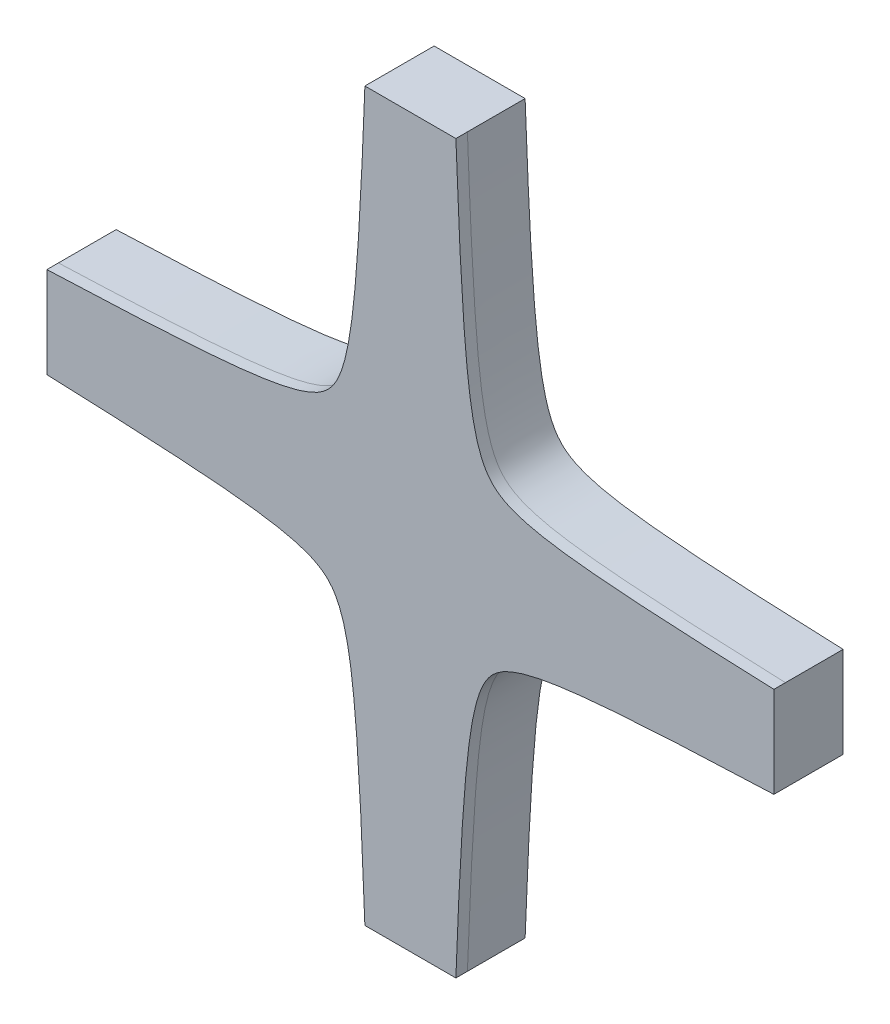
SolidWorks part; units mm, degrees
ref_plane "Front Plane" through (0, 0, 0) normal (0, 0, 1) x (1, 0, 0)
ref_plane "Top Plane" through (0, 0, 0) normal (0, 1, 0) x (1, 0, 0)
ref_plane "Right Plane" through (0, 0, 0) normal (1, 0, 0) x (0, 0, -1)
sketch "Sketch1" plane through (0, 0, 0) normal (0, 0, 1) x (1, 0, 0)
  line L0 (-66.0929, 6.6772) -> (-66.0929, 14.5621)
  line L1 (-66.0929, 6.6772) -> (-66.0929, -1.2077)
  line L2 (-3.0929, -56.3228) -> (-10.9779, -56.3228)
  line L3 (-3.0929, 66.6772) -> (1.9071, 66.6772)
  line L4 (-3.0929, 66.6772) -> (-8.0929, 66.6772)
  line L5 (-63.0929, 6.6772) -> (-63.0929, 11.6772)
  line L6 (-63.0929, 6.6772) -> (-63.0929, 1.6772)
  line L7 (56.9071, 6.6772) -> (56.9071, 11.6772)
  line L8 (56.9071, 6.6772) -> (56.9071, 1.6772)
  line L9 (-3.0929, -53.3228) -> (1.9071, -53.3228)
  line L10 (-3.0929, -53.3228) -> (-8.0929, -53.3228)
  line L11 (-3.0929, -56.3228) -> (4.792, -56.3228)
  line L12 (59.9071, 6.6772) -> (59.9071, -1.2077)
  line L13 (59.9071, 6.6772) -> (59.9071, 14.5621)
  line L14 (-3.0929, 69.6772) -> (4.792, 69.6772)
  line L15 (-3.0929, 69.6772) -> (-10.9779, 69.6772)
  conic Q0 (-8.0929, 66.6772) -> (-63.0929, 11.6772) control (-10.164, 13.7483) rho 0.8
  conic Q1 (-63.0929, 1.6772) -> (-8.0929, -53.3228) control (-10.164, -0.3939) rho 0.8
  conic Q2 (1.9071, -53.3228) -> (56.9071, 1.6772) control (3.9781, -0.3939) rho 0.8
  conic Q3 (56.9071, 11.6772) -> (1.9071, 66.6772) control (3.9781, 13.7483) rho 0.8
  spline S0 degree 1 poles (-10.9779, 69.6772) (-66.0929, 14.5621) knots 0 0 1 1 construction
  spline S1 degree 1 poles (-66.0929, -1.2077) (-10.9779, -56.3228) knots 0 0 1 1 construction
  spline S2 degree 1 poles (4.792, -56.3228) (59.9071, -1.2077) knots 0 0 1 1 construction
  spline S3 degree 1 poles (59.9071, 14.5621) (4.792, 69.6772) knots 0 0 1 1 construction
  spline S4 degree 3 poles (-10.9779, 69.6772) (-11.0215, 68.561) (-11.11, 66.2805) (-11.2364, 63.1476) (-11.3563, 60.3371) (-11.5092, 56.9331) (-11.6891, 53.2462) (-11.8923, 49.5138) (-12.0863, 46.3255) (-12.336, 42.6549) (-12.6368, 38.943) (-12.9903, 35.4465) (-13.3431, 32.6425) (-13.6999, 30.355) (-14.1844, 27.8371) (-14.8116, 25.4707) (-15.6029, 23.4568) (-16.435, 22.012) (-17.341, 20.9252) (-18.4277, 20.0193) (-19.8725, 19.1872) (-21.8865, 18.3958) (-24.2529, 17.7686) (-26.7707, 17.2841) (-29.0583, 16.9274) (-31.8623, 16.5745) (-35.3587, 16.221) (-39.0707, 15.9203) (-42.7413, 15.6705) (-45.9295, 15.4766) (-49.662, 15.2734) (-53.3488, 15.0934) (-56.7529, 14.9405) (-59.5634, 14.8207) (-62.6963, 14.6942) (-64.9767, 14.6058) (-66.0929, 14.5621) knots -0.006808 -0.006808 -0.006808 -0.006808 0.001111 0.00903 0.016949 0.024868 0.040705 0.056543 0.072381 0.088219 0.119894 0.15157 0.183245 0.214921 0.246596 0.309947 0.373298 0.436649 0.5 0.563351 0.626702 0.690053 0.753404 0.785079 0.816755 0.84843 0.880106 0.911781 0.927619 0.943457 0.959295 0.975132 0.983051 0.99097 0.998889 1.006808 1.006808 1.006808 1.006808
  spline S5 degree 3 poles (-66.0929, -1.2077) (-64.9767, -1.2514) (-62.6963, -1.3399) (-59.5634, -1.4663) (-56.7529, -1.5861) (-53.3488, -1.739) (-49.662, -1.919) (-45.9295, -2.1222) (-42.7413, -2.3161) (-39.0707, -2.5659) (-35.3587, -2.8666) (-31.8623, -3.2202) (-29.0583, -3.573) (-26.7707, -3.9297) (-24.2529, -4.4142) (-21.8865, -5.0414) (-19.8725, -5.8328) (-18.4277, -6.6649) (-17.341, -7.5709) (-16.435, -8.6576) (-15.6029, -10.1024) (-14.8116, -12.1164) (-14.1844, -14.4827) (-13.6999, -17.0006) (-13.3431, -19.2881) (-12.9903, -22.0922) (-12.6368, -25.5886) (-12.336, -29.3005) (-12.0863, -32.9711) (-11.8923, -36.1594) (-11.6891, -39.8918) (-11.5092, -43.5787) (-11.3563, -46.9828) (-11.2364, -49.7932) (-11.11, -52.9262) (-11.0215, -55.2066) (-10.9779, -56.3228) knots -0.006808 -0.006808 -0.006808 -0.006808 0.001111 0.00903 0.016949 0.024868 0.040705 0.056543 0.072381 0.088219 0.119894 0.15157 0.183245 0.214921 0.246596 0.309947 0.373298 0.436649 0.5 0.563351 0.626702 0.690053 0.753404 0.785079 0.816755 0.84843 0.880106 0.911781 0.927619 0.943457 0.959295 0.975132 0.983051 0.99097 0.998889 1.006808 1.006808 1.006808 1.006808
  spline S6 degree 3 poles (4.792, -56.3228) (4.8356, -55.2066) (4.9241, -52.9262) (5.0505, -49.7932) (5.1704, -46.9828) (5.3233, -43.5787) (5.5032, -39.8918) (5.7064, -36.1594) (5.9004, -32.9711) (6.1501, -29.3005) (6.4509, -25.5886) (6.8044, -22.0922) (7.1572, -19.2881) (7.514, -17.0006) (7.9985, -14.4827) (8.6257, -12.1164) (9.417, -10.1024) (10.2491, -8.6576) (11.1551, -7.5709) (12.2418, -6.6649) (13.6866, -5.8328) (15.7006, -5.0414) (18.067, -4.4142) (20.5848, -3.9297) (22.8724, -3.573) (25.6764, -3.2202) (29.1728, -2.8666) (32.8848, -2.5659) (36.5554, -2.3161) (39.7436, -2.1222) (43.4761, -1.919) (47.1629, -1.739) (50.567, -1.5861) (53.3775, -1.4663) (56.5104, -1.3399) (58.7908, -1.2514) (59.9071, -1.2077) knots -0.006808 -0.006808 -0.006808 -0.006808 0.001111 0.00903 0.016949 0.024868 0.040705 0.056543 0.072381 0.088219 0.119894 0.15157 0.183245 0.214921 0.246596 0.309947 0.373298 0.436649 0.5 0.563351 0.626702 0.690053 0.753404 0.785079 0.816755 0.84843 0.880106 0.911781 0.927619 0.943457 0.959295 0.975132 0.983051 0.99097 0.998889 1.006808 1.006808 1.006808 1.006808
  spline S7 degree 3 poles (59.9071, 14.5621) (58.7908, 14.6058) (56.5104, 14.6942) (53.3775, 14.8207) (50.567, 14.9405) (47.1629, 15.0934) (43.4761, 15.2734) (39.7436, 15.4766) (36.5554, 15.6705) (32.8848, 15.9203) (29.1728, 16.221) (25.6764, 16.5745) (22.8724, 16.9274) (20.5848, 17.2841) (18.067, 17.7686) (15.7006, 18.3958) (13.6866, 19.1872) (12.2418, 20.0193) (11.1551, 20.9252) (10.2491, 22.012) (9.417, 23.4568) (8.6257, 25.4707) (7.9985, 27.8371) (7.514, 30.355) (7.1572, 32.6425) (6.8044, 35.4465) (6.4509, 38.943) (6.1501, 42.6549) (5.9004, 46.3255) (5.7064, 49.5138) (5.5032, 53.2462) (5.3233, 56.9331) (5.1704, 60.3371) (5.0505, 63.1476) (4.9241, 66.2805) (4.8356, 68.561) (4.792, 69.6772) knots -0.006808 -0.006808 -0.006808 -0.006808 0.001111 0.00903 0.016949 0.024868 0.040705 0.056543 0.072381 0.088219 0.119894 0.15157 0.183245 0.214921 0.246596 0.309947 0.373298 0.436649 0.5 0.563351 0.626702 0.690053 0.753404 0.785079 0.816755 0.84843 0.880106 0.911781 0.927619 0.943457 0.959295 0.975132 0.983051 0.99097 0.998889 1.006808 1.006808 1.006808 1.006808
  dimension "D1" = 3
extrude "Boss-Extrude1" add sketch "Sketch1" along normal blind 10
sketch "Sketch4" plane through (0, 0, 10) normal (0, 0, 1) x (1, 0, 0)
  line L14 (59.9071, -1.2077) -> (59.9071, 14.5621)
  line L15 (-10.9779, -56.3228) -> (4.792, -56.3228)
  line L16 (-66.0929, 14.5621) -> (-66.0929, -1.2077)
  line L17 (4.792, 69.6772) -> (-10.9779, 69.6772)
  line L18 (59.9071, -1.2077) -> (59.9071, 14.5621)
  line L19 (-10.9779, -56.3228) -> (4.792, -56.3228)
  line L20 (-66.0929, 14.5621) -> (-66.0929, -1.2077)
  line L21 (4.792, 69.6772) -> (-10.9779, 69.6772)
  spline S31 degree 3 poles (333.6807, -3948.7714) (411.161, 40.1752) (231.1528, 7.4827) (51.6403, 14.8935) (49.5741, 14.9833) (43.3766, 15.2724) (39.2464, 15.4881) (33.0574, 15.9095) (30.9955, 16.0666) (26.8757, 16.4451) (24.817, 16.6645) (21.7382, 17.1007) (20.7163, 17.264) (18.6871, 17.6505) (17.6795, 17.8729) (16.1882, 18.2887) (15.6946, 18.4413) (14.7171, 18.7874) (14.2315, 18.9815) (13.2838, 19.4289) (12.8272, 19.6795) (12.179, 20.1126) (11.9691, 20.2665) (11.5634, 20.5964) (11.3666, 20.7737) (10.8112, 21.3299) (10.4861, 21.7341) (10.0538, 22.3812) (9.9188, 22.6036) (9.6645, 23.0601) (9.545, 23.2947) (9.2107, 24.0034) (9.0182, 24.4848) (8.6729, 25.4595) (8.5203, 25.9527) (8.1039, 27.4448) (7.8806, 28.4556) (7.4924, 30.4946) (7.3288, 31.52) (6.8934, 34.5959) (6.6743, 36.6521) (6.2962, 40.7692) (6.1392, 42.8302) (5.718, 49.0172) (5.5023, 53.147) (5.2131, 59.3443) (5.1233, 61.4106) (-2.2806, 240.7573) (30.38, 419.6429) (-3951.0017, 437.3325) knots -5.304164 -5.304164 -5.304164 -5.304164 0.0625 0.0625 0.125 0.125 0.25 0.25 0.3125 0.3125 0.375 0.375 0.40625 0.40625 0.4375 0.4375 0.453125 0.453125 0.46875 0.46875 0.484375 0.484375 0.492187 0.492187 0.5 0.5 0.515625 0.515625 0.523437 0.523437 0.53125 0.53125 0.546875 0.546875 0.5625 0.5625 0.59375 0.59375 0.625 0.625 0.6875 0.6875 0.75 0.75 0.875 0.875 0.9375 0.9375 6.29912 6.29912 6.29912 6.29912 only from (59.9071, 14.5621) to (4.792, 69.6772)
  spline S32 degree 3 poles (-3958.5416, -330.0965) (30.405, -407.5768) (-2.2875, -227.5686) (5.1233, -48.0561) (5.2131, -45.9898) (5.5023, -39.7923) (5.718, -35.6622) (6.1393, -29.4732) (6.2965, -27.4112) (6.675, -23.2915) (6.8944, -21.2327) (7.3305, -18.1539) (7.4939, -17.132) (7.8804, -15.1028) (8.1027, -14.0953) (8.5186, -12.604) (8.6712, -12.1103) (9.0173, -11.1329) (9.2114, -10.6473) (9.6587, -9.6995) (9.9094, -9.243) (10.3424, -8.5948) (10.4964, -8.3849) (10.8263, -7.9792) (11.0036, -7.7824) (11.5598, -7.2269) (11.964, -6.9018) (12.611, -6.4695) (12.8335, -6.3346) (13.2899, -6.0803) (13.5246, -5.9607) (14.2333, -5.6265) (14.7147, -5.434) (15.6894, -5.0887) (16.1826, -4.936) (17.6747, -4.5196) (18.6855, -4.2964) (20.7244, -3.9081) (21.7498, -3.7445) (24.8258, -3.3091) (26.882, -3.0901) (30.999, -2.7119) (33.0601, -2.5549) (39.2471, -2.1337) (43.3768, -1.918) (49.5741, -1.6289) (51.6405, -1.5391) (230.9872, 5.8648) (409.8728, -26.7957) (427.5624, 3954.5859) knots -5.304164 -5.304164 -5.304164 -5.304164 0.0625 0.0625 0.125 0.125 0.25 0.25 0.3125 0.3125 0.375 0.375 0.40625 0.40625 0.4375 0.4375 0.453125 0.453125 0.46875 0.46875 0.484375 0.484375 0.492187 0.492187 0.5 0.5 0.515625 0.515625 0.523437 0.523437 0.53125 0.53125 0.546875 0.546875 0.5625 0.5625 0.59375 0.59375 0.625 0.625 0.6875 0.6875 0.75 0.75 0.875 0.875 0.9375 0.9375 6.29912 6.29912 6.29912 6.29912 only from (4.792, -56.3228) to (59.9071, -1.2077)
  spline S33 degree 3 poles (-339.8666, 3962.1258) (-417.3469, -26.8208) (-237.3387, 5.8717) (-57.8262, -1.5391) (-55.76, -1.6289) (-49.5625, -1.9181) (-45.4323, -2.1338) (-39.2433, -2.5551) (-37.1814, -2.7122) (-33.0616, -3.0907) (-31.0029, -3.3101) (-27.9241, -3.7463) (-26.9022, -3.9096) (-24.8729, -4.2962) (-23.8654, -4.5185) (-22.3741, -4.9343) (-21.8805, -5.087) (-20.903, -5.433) (-20.4174, -5.6271) (-19.4697, -6.0745) (-19.0131, -6.3251) (-18.3649, -6.7582) (-18.155, -6.9121) (-17.7493, -7.2421) (-17.5525, -7.4193) (-16.9971, -7.9756) (-16.672, -8.3797) (-16.2397, -9.0268) (-16.1047, -9.2492) (-15.8504, -9.7057) (-15.7309, -9.9403) (-15.3966, -10.649) (-15.2041, -11.1305) (-14.8588, -12.1051) (-14.7062, -12.5984) (-14.2898, -14.0904) (-14.0665, -15.1013) (-13.6783, -17.1402) (-13.5147, -18.1656) (-13.0793, -21.2415) (-12.8602, -23.2977) (-12.4821, -27.4148) (-12.3251, -29.4758) (-11.9039, -35.6628) (-11.6882, -39.7926) (-11.399, -45.9899) (-11.3092, -48.0562) (-3.9053, -227.4029) (-36.5659, -406.2885) (3944.8158, -423.9782) knots -5.304164 -5.304164 -5.304164 -5.304164 0.0625 0.0625 0.125 0.125 0.25 0.25 0.3125 0.3125 0.375 0.375 0.40625 0.40625 0.4375 0.4375 0.453125 0.453125 0.46875 0.46875 0.484375 0.484375 0.492187 0.492187 0.5 0.5 0.515625 0.515625 0.523437 0.523437 0.53125 0.53125 0.546875 0.546875 0.5625 0.5625 0.59375 0.59375 0.625 0.625 0.6875 0.6875 0.75 0.75 0.875 0.875 0.9375 0.9375 6.29912 6.29912 6.29912 6.29912 only from (-66.0929, -1.2077) to (-10.9779, -56.3228)
  spline S34 degree 3 poles (3952.3557, 343.4509) (-36.5909, 420.9311) (-3.8984, 240.923) (-11.3092, 61.4104) (-11.399, 59.3442) (-11.6882, 53.1467) (-11.9039, 49.0166) (-12.3252, 42.8276) (-12.4824, 40.7656) (-12.8609, 36.6459) (-13.0803, 34.5871) (-13.5164, 31.5083) (-13.6798, 30.4864) (-14.0663, 28.4572) (-14.2886, 27.4496) (-14.7045, 25.9584) (-14.8571, 25.4647) (-15.2032, 24.4873) (-15.3973, 24.0016) (-15.8446, 23.0539) (-16.0953, 22.5973) (-16.5283, 21.9492) (-16.6822, 21.7392) (-17.0122, 21.3336) (-17.1895, 21.1367) (-17.7457, 20.5813) (-18.1499, 20.2562) (-18.7969, 19.8239) (-19.0194, 19.6889) (-19.4758, 19.4347) (-19.7105, 19.3151) (-20.4192, 18.9808) (-20.9006, 18.7884) (-21.8753, 18.4431) (-22.3685, 18.2904) (-23.8606, 17.874) (-24.8714, 17.6508) (-26.9103, 17.2625) (-27.9357, 17.0989) (-31.0117, 16.6635) (-33.0679, 16.4445) (-37.1849, 16.0663) (-39.246, 15.9093) (-45.433, 15.4881) (-49.5627, 15.2724) (-55.76, 14.9833) (-57.8264, 14.8935) (-237.1731, 7.4895) (-416.0587, 40.1501) (-433.7483, -3941.2315) knots -5.304164 -5.304164 -5.304164 -5.304164 0.0625 0.0625 0.125 0.125 0.25 0.25 0.3125 0.3125 0.375 0.375 0.40625 0.40625 0.4375 0.4375 0.453125 0.453125 0.46875 0.46875 0.484375 0.484375 0.492187 0.492187 0.5 0.5 0.515625 0.515625 0.523437 0.523437 0.53125 0.53125 0.546875 0.546875 0.5625 0.5625 0.59375 0.59375 0.625 0.625 0.6875 0.6875 0.75 0.75 0.875 0.875 0.9375 0.9375 6.29912 6.29912 6.29912 6.29912 only from (-10.9779, 69.6772) to (-66.0929, 14.5621)
  spline S35 degree 3 poles (59.9071, 14.5621) (57.8402, 14.643) (55.7734, 14.7229) (51.6403, 14.8935) (49.5741, 14.9833) (43.3766, 15.2724) (39.2464, 15.4881) (33.0574, 15.9095) (30.9955, 16.0666) (26.8757, 16.4451) (24.817, 16.6645) (21.7382, 17.1007) (20.7163, 17.264) (18.6871, 17.6505) (17.6795, 17.8729) (16.1882, 18.2887) (15.6946, 18.4413) (14.7171, 18.7874) (14.2315, 18.9815) (13.2838, 19.4289) (12.8272, 19.6795) (12.179, 20.1126) (11.9691, 20.2665) (11.5634, 20.5964) (11.3666, 20.7737) (10.8112, 21.3299) (10.4861, 21.7341) (10.0538, 22.3812) (9.9188, 22.6036) (9.6645, 23.0601) (9.545, 23.2947) (9.2107, 24.0034) (9.0182, 24.4848) (8.6729, 25.4595) (8.5203, 25.9527) (8.1039, 27.4448) (7.8806, 28.4556) (7.4924, 30.4946) (7.3288, 31.52) (6.8934, 34.5959) (6.6743, 36.6521) (6.2962, 40.7692) (6.1392, 42.8302) (5.718, 49.0172) (5.5023, 53.147) (5.2131, 59.3443) (5.1233, 61.4106) (4.9527, 65.5437) (4.8728, 67.6105) (4.792, 69.6772) knots 0 0 0 0 0.0625 0.0625 0.125 0.125 0.25 0.25 0.3125 0.3125 0.375 0.375 0.40625 0.40625 0.4375 0.4375 0.453125 0.453125 0.46875 0.46875 0.484375 0.484375 0.492187 0.492187 0.5 0.5 0.515625 0.515625 0.523437 0.523437 0.53125 0.53125 0.546875 0.546875 0.5625 0.5625 0.59375 0.59375 0.625 0.625 0.6875 0.6875 0.75 0.75 0.875 0.875 0.9375 0.9375 1 1 1 1
  spline S36 degree 3 poles (4.792, -56.3228) (4.8728, -54.256) (4.9527, -52.1891) (5.1233, -48.0561) (5.2131, -45.9898) (5.5023, -39.7923) (5.718, -35.6622) (6.1393, -29.4732) (6.2965, -27.4112) (6.675, -23.2915) (6.8944, -21.2327) (7.3305, -18.1539) (7.4939, -17.132) (7.8804, -15.1028) (8.1027, -14.0953) (8.5186, -12.604) (8.6712, -12.1103) (9.0173, -11.1329) (9.2114, -10.6473) (9.6587, -9.6995) (9.9094, -9.243) (10.3424, -8.5948) (10.4964, -8.3849) (10.8263, -7.9792) (11.0036, -7.7824) (11.5598, -7.2269) (11.964, -6.9018) (12.611, -6.4695) (12.8335, -6.3346) (13.2899, -6.0803) (13.5246, -5.9607) (14.2333, -5.6265) (14.7147, -5.434) (15.6894, -5.0887) (16.1826, -4.936) (17.6747, -4.5196) (18.6855, -4.2964) (20.7244, -3.9081) (21.7498, -3.7445) (24.8258, -3.3091) (26.882, -3.0901) (30.999, -2.7119) (33.0601, -2.5549) (39.2471, -2.1337) (43.3768, -1.918) (49.5741, -1.6289) (51.6405, -1.5391) (55.7736, -1.3685) (57.8403, -1.2886) (59.9071, -1.2077) knots 0 0 0 0 0.0625 0.0625 0.125 0.125 0.25 0.25 0.3125 0.3125 0.375 0.375 0.40625 0.40625 0.4375 0.4375 0.453125 0.453125 0.46875 0.46875 0.484375 0.484375 0.492187 0.492187 0.5 0.5 0.515625 0.515625 0.523437 0.523437 0.53125 0.53125 0.546875 0.546875 0.5625 0.5625 0.59375 0.59375 0.625 0.625 0.6875 0.6875 0.75 0.75 0.875 0.875 0.9375 0.9375 1 1 1 1
  spline S37 degree 3 poles (-66.0929, -1.2077) (-64.0261, -1.2886) (-61.9593, -1.3685) (-57.8262, -1.5391) (-55.76, -1.6289) (-49.5625, -1.9181) (-45.4323, -2.1338) (-39.2433, -2.5551) (-37.1814, -2.7122) (-33.0616, -3.0907) (-31.0029, -3.3101) (-27.9241, -3.7463) (-26.9022, -3.9096) (-24.8729, -4.2962) (-23.8654, -4.5185) (-22.3741, -4.9343) (-21.8805, -5.087) (-20.903, -5.433) (-20.4174, -5.6271) (-19.4697, -6.0745) (-19.0131, -6.3251) (-18.3649, -6.7582) (-18.155, -6.9121) (-17.7493, -7.2421) (-17.5525, -7.4193) (-16.9971, -7.9756) (-16.672, -8.3797) (-16.2397, -9.0268) (-16.1047, -9.2492) (-15.8504, -9.7057) (-15.7309, -9.9403) (-15.3966, -10.649) (-15.2041, -11.1305) (-14.8588, -12.1051) (-14.7062, -12.5984) (-14.2898, -14.0904) (-14.0665, -15.1013) (-13.6783, -17.1402) (-13.5147, -18.1656) (-13.0793, -21.2415) (-12.8602, -23.2977) (-12.4821, -27.4148) (-12.3251, -29.4758) (-11.9039, -35.6628) (-11.6882, -39.7926) (-11.399, -45.9899) (-11.3092, -48.0562) (-11.1386, -52.1893) (-11.0587, -54.2561) (-10.9779, -56.3228) knots 0 0 0 0 0.0625 0.0625 0.125 0.125 0.25 0.25 0.3125 0.3125 0.375 0.375 0.40625 0.40625 0.4375 0.4375 0.453125 0.453125 0.46875 0.46875 0.484375 0.484375 0.492187 0.492187 0.5 0.5 0.515625 0.515625 0.523437 0.523437 0.53125 0.53125 0.546875 0.546875 0.5625 0.5625 0.59375 0.59375 0.625 0.625 0.6875 0.6875 0.75 0.75 0.875 0.875 0.9375 0.9375 1 1 1 1
  spline S38 degree 3 poles (-10.9779, 69.6772) (-11.0587, 67.6104) (-11.1386, 65.5435) (-11.3092, 61.4104) (-11.399, 59.3442) (-11.6882, 53.1467) (-11.9039, 49.0166) (-12.3252, 42.8276) (-12.4824, 40.7656) (-12.8609, 36.6459) (-13.0803, 34.5871) (-13.5164, 31.5083) (-13.6798, 30.4864) (-14.0663, 28.4572) (-14.2886, 27.4496) (-14.7045, 25.9584) (-14.8571, 25.4647) (-15.2032, 24.4873) (-15.3973, 24.0016) (-15.8446, 23.0539) (-16.0953, 22.5973) (-16.5283, 21.9492) (-16.6822, 21.7392) (-17.0122, 21.3336) (-17.1895, 21.1367) (-17.7457, 20.5813) (-18.1499, 20.2562) (-18.7969, 19.8239) (-19.0194, 19.6889) (-19.4758, 19.4347) (-19.7105, 19.3151) (-20.4192, 18.9808) (-20.9006, 18.7884) (-21.8753, 18.4431) (-22.3685, 18.2904) (-23.8606, 17.874) (-24.8714, 17.6508) (-26.9103, 17.2625) (-27.9357, 17.0989) (-31.0117, 16.6635) (-33.0679, 16.4445) (-37.1849, 16.0663) (-39.246, 15.9093) (-45.433, 15.4881) (-49.5627, 15.2724) (-55.76, 14.9833) (-57.8264, 14.8935) (-61.9595, 14.7228) (-64.0262, 14.643) (-66.0929, 14.5621) knots 0 0 0 0 0.0625 0.0625 0.125 0.125 0.25 0.25 0.3125 0.3125 0.375 0.375 0.40625 0.40625 0.4375 0.4375 0.453125 0.453125 0.46875 0.46875 0.484375 0.484375 0.492187 0.492187 0.5 0.5 0.515625 0.515625 0.523437 0.523437 0.53125 0.53125 0.546875 0.546875 0.5625 0.5625 0.59375 0.59375 0.625 0.625 0.6875 0.6875 0.75 0.75 0.875 0.875 0.9375 0.9375 1 1 1 1
  dimension "D1" = 3
extrude "Boss-Extrude2" add sketch "Sketch4" along normal blind 2
sketch "Sketch5" plane through (0, 0, 10) normal (0, 0, -1) x (-1, 0, 0)
  line L0 (7.9919, 7.6772) -> (18.0929, 7.6772)
  line L1 (2.0929, 11.5762) -> (2.0929, 21.6772)
  line L2 (4.0929, 11.5762) -> (4.0929, 21.6772)
  line L3 (7.9919, 5.6772) -> (18.0929, 5.6772)
  line L4 (4.0929, 21.6772) -> (11.5185, 21.6772)
  line L5 (11.5185, 21.6772) -> (10.607, 24.0051)
  line L6 (4.0929, 24.0051) -> (4.0929, 26.5051)
  line L7 (2.0929, 21.6772) -> (-5.3326, 21.6772)
  line L8 (-5.3326, 21.6772) -> (-4.4211, 24.0051)
  line L9 (-4.4211, 24.0051) -> (2.0929, 24.0051)
  line L10 (4.0929, 26.5051) -> (9.906, 26.5051)
  line L12 (9.906, 26.5051) -> (9.3922, 28.9517)
  line L13 (2.0929, 24.0051) -> (2.0929, 26.5051)
  line L14 (2.0929, 26.5051) -> (-3.7201, 26.5051)
  line L15 (-3.7201, 26.5051) -> (-3.2063, 28.9517)
  line L16 (-3.2063, 28.9517) -> (2.0929, 28.9517)
  line L17 (4.0929, 24.0051) -> (10.607, 24.0051)
  line L18 (4.0929, 28.9517) -> (4.0929, 31.4517)
  line L19 (4.0929, 31.4517) -> (8.9807, 31.4517)
  line L20 (2.0929, 28.9517) -> (2.0929, 31.4517)
  line L21 (2.0929, 31.4517) -> (-2.7948, 31.4517)
  line L22 (8.9807, 31.4517) -> (8.65, 33.9298)
  line L23 (8.65, 33.9298) -> (4.0929, 33.9298)
  line L24 (-2.4641, 33.9298) -> (-2.7948, 31.4517)
  line L25 (4.0929, 33.9298) -> (4.0929, 36.4298)
  line L26 (4.0929, 36.4298) -> (8.3714, 36.4298)
  line L27 (2.0929, 33.9298) -> (2.0929, 36.4298)
  line L28 (2.0929, 36.4298) -> (-2.1855, 36.4298)
  line L29 (8.3714, 36.4298) -> (8.1341, 38.9185)
  line L30 (8.1341, 38.9185) -> (4.0929, 38.9185)
  line L31 (-1.9482, 38.9185) -> (-2.1855, 36.4298)
  line L32 (4.0929, 38.9185) -> (4.0929, 41.4185)
  line L33 (4.0929, 41.4185) -> (7.926, 41.4185)
  line L34 (7.926, 41.4185) -> (7.7416, 43.9117)
  line L35 (2.0929, 38.9185) -> (2.0929, 41.4185)
  line L36 (2.0929, 41.4185) -> (-1.7401, 41.4185)
  line L37 (-1.7401, 41.4185) -> (-1.5557, 43.9117)
  line L38 (-1.5557, 43.9117) -> (2.0929, 43.9117)
  line L39 (4.0929, 43.9117) -> (4.0929, 46.4117)
  line L40 (4.0929, 46.4117) -> (7.5751, 46.4117)
  line L41 (7.5751, 46.4117) -> (7.4236, 48.9071)
  line L42 (2.0929, 43.9117) -> (2.0929, 46.4117)
  line L43 (2.0929, 46.4117) -> (-1.3892, 46.4117)
  line L44 (-1.3892, 46.4117) -> (-1.2377, 48.9071)
  line L45 (-1.2377, 48.9071) -> (2.0929, 48.9071)
  line L46 (4.0929, 48.9071) -> (4.0929, 51.4071)
  line L47 (4.0929, 51.4071) -> (7.2836, 51.4071)
  line L48 (7.2836, 51.4071) -> (7.1536, 53.9037)
  line L49 (2.0929, 48.9071) -> (2.0929, 51.4071)
  line L50 (2.0929, 51.4071) -> (-1.0977, 51.4071)
  line L51 (-1.0977, 51.4071) -> (-0.9677, 53.9037)
  line L52 (-0.9677, 53.9037) -> (2.0929, 53.9037)
  line L53 (4.0929, 53.9037) -> (4.0929, 56.4037)
  line L54 (4.0929, 56.4037) -> (7.0316, 56.4037)
  line L55 (7.0316, 56.4037) -> (6.9165, 58.901)
  line L56 (2.0929, 53.9037) -> (2.0929, 56.4037)
  line L57 (2.0929, 56.4037) -> (-0.8457, 56.4037)
  line L58 (-0.8457, 56.4037) -> (-0.7306, 58.901)
  line L59 (-0.7306, 58.901) -> (2.0929, 58.901)
  line L60 (4.0929, 58.901) -> (4.0929, 61.401)
  line L61 (4.0929, 61.401) -> (6.8071, 61.401)
  line L62 (6.8071, 61.401) -> (6.7028, 63.8989)
  line L63 (2.0929, 58.901) -> (2.0929, 61.401)
  line L64 (2.0929, 61.401) -> (-0.6212, 61.401)
  line L65 (-0.6212, 61.401) -> (-0.5169, 63.8989)
  line L66 (-0.5169, 63.8989) -> (6.7028, 63.8989)
  line L67 (4.0929, 58.901) -> (6.9165, 58.901)
  line L68 (4.0929, 53.9037) -> (7.1536, 53.9037)
  line L69 (4.0929, 48.9071) -> (7.4236, 48.9071)
  line L70 (4.0929, 43.9117) -> (7.7416, 43.9117)
  line L71 (2.0929, 38.9185) -> (-1.9482, 38.9185)
  line L72 (2.0929, 33.9298) -> (-2.4641, 33.9298)
  line L73 (4.0929, 28.9517) -> (9.3922, 28.9517)
  line L74 (18.0929, 5.6772) -> (18.0929, -1.7484)
  line L75 (18.0929, -1.7484) -> (20.4209, -0.8369)
  line L76 (20.4209, 5.6772) -> (22.9209, 5.6772)
  line L77 (18.0929, 7.6772) -> (18.0929, 15.1028)
  line L78 (18.0929, 15.1028) -> (20.4209, 14.1913)
  line L79 (20.4209, 14.1913) -> (20.4209, 7.6772)
  line L80 (22.9209, 5.6772) -> (22.9209, -0.1359)
  line L81 (22.9209, -0.1359) -> (25.3675, 0.378)
  line L82 (20.4209, 7.6772) -> (22.9209, 7.6772)
  line L83 (22.9209, 7.6772) -> (22.9209, 13.4902)
  line L84 (22.9209, 13.4902) -> (25.3675, 12.9764)
  line L85 (25.3675, 12.9764) -> (25.3675, 7.6772)
  line L86 (20.4209, 5.6772) -> (20.4209, -0.8369)
  line L87 (25.3675, 5.6772) -> (27.8675, 5.6772)
  line L88 (27.8675, 5.6772) -> (27.8675, 0.7894)
  line L89 (25.3675, 7.6772) -> (27.8675, 7.6772)
  line L90 (27.8675, 7.6772) -> (27.8675, 12.565)
  line L91 (27.8675, 0.7894) -> (30.3455, 1.1201)
  line L92 (30.3455, 1.1201) -> (30.3455, 5.6772)
  line L93 (30.3455, 12.2343) -> (27.8675, 12.565)
  line L94 (30.3455, 5.6772) -> (32.8455, 5.6772)
  line L95 (32.8455, 5.6772) -> (32.8455, 1.3988)
  line L96 (30.3455, 7.6772) -> (32.8455, 7.6772)
  line L97 (32.8455, 7.6772) -> (32.8455, 11.9556)
  line L98 (32.8455, 1.3988) -> (35.3342, 1.6361)
  line L99 (35.3342, 1.6361) -> (35.3342, 5.6772)
  line L100 (35.3342, 11.7183) -> (32.8455, 11.9556)
  line L101 (35.3342, 5.6772) -> (37.8342, 5.6772)
  line L102 (37.8342, 5.6772) -> (37.8342, 1.8442)
  line L103 (37.8342, 1.8442) -> (40.3274, 2.0285)
  line L104 (35.3342, 7.6772) -> (37.8342, 7.6772)
  line L105 (37.8342, 7.6772) -> (37.8342, 11.5102)
  line L106 (37.8342, 11.5102) -> (40.3274, 11.3259)
  line L107 (40.3274, 11.3259) -> (40.3274, 7.6772)
  line L108 (40.3274, 5.6772) -> (42.8274, 5.6772)
  line L109 (42.8274, 5.6772) -> (42.8274, 2.195)
  line L110 (42.8274, 2.195) -> (45.3228, 2.3466)
  line L111 (40.3274, 7.6772) -> (42.8274, 7.6772)
  line L112 (42.8274, 7.6772) -> (42.8274, 11.1594)
  line L113 (42.8274, 11.1594) -> (45.3228, 11.0078)
  line L114 (45.3228, 11.0078) -> (45.3228, 7.6772)
  line L115 (45.3228, 5.6772) -> (47.8228, 5.6772)
  line L116 (47.8228, 5.6772) -> (47.8228, 2.4865)
  line L117 (47.8228, 2.4865) -> (50.3195, 2.6165)
  line L118 (45.3228, 7.6772) -> (47.8228, 7.6772)
  line L119 (47.8228, 7.6772) -> (47.8228, 10.8679)
  line L120 (47.8228, 10.8679) -> (50.3195, 10.7378)
  line L121 (50.3195, 10.7378) -> (50.3195, 7.6772)
  line L122 (50.3195, 5.6772) -> (52.8195, 5.6772)
  line L123 (52.8195, 5.6772) -> (52.8195, 2.7386)
  line L124 (52.8195, 2.7386) -> (55.3168, 2.8537)
  line L125 (50.3195, 7.6772) -> (52.8195, 7.6772)
  line L126 (52.8195, 7.6772) -> (52.8195, 10.6158)
  line L127 (52.8195, 10.6158) -> (55.3168, 10.5007)
  line L128 (55.3168, 10.5007) -> (55.3168, 7.6772)
  line L129 (55.3168, 5.6772) -> (57.8168, 5.6772)
  line L130 (57.8168, 5.6772) -> (57.8168, 2.963)
  line L131 (57.8168, 2.963) -> (60.3146, 3.0673)
  line L132 (55.3168, 7.6772) -> (57.8168, 7.6772)
  line L133 (57.8168, 7.6772) -> (57.8168, 10.3914)
  line L134 (57.8168, 10.3914) -> (60.3146, 10.287)
  line L135 (60.3146, 10.287) -> (60.3146, 3.0673)
  line L136 (55.3168, 5.6772) -> (55.3168, 2.8537)
  line L137 (50.3195, 5.6772) -> (50.3195, 2.6165)
  line L138 (45.3228, 5.6772) -> (45.3228, 2.3466)
  line L139 (40.3274, 5.6772) -> (40.3274, 2.0285)
  line L140 (35.3342, 7.6772) -> (35.3342, 11.7183)
  line L141 (30.3455, 7.6772) -> (30.3455, 12.2343)
  line L142 (25.3675, 5.6772) -> (25.3675, 0.378)
  line L143 (4.0929, 1.7782) -> (4.0929, -8.3228)
  line L144 (2.0929, 1.7782) -> (2.0929, -8.3228)
  line L145 (2.0929, -8.3228) -> (-5.3326, -8.3228)
  line L146 (-5.3326, -8.3228) -> (-4.4211, -10.6507)
  line L147 (2.0929, -10.6507) -> (2.0929, -13.1507)
  line L148 (4.0929, -8.3228) -> (11.5185, -8.3228)
  line L149 (11.5185, -8.3228) -> (10.607, -10.6507)
  line L150 (10.607, -10.6507) -> (4.0929, -10.6507)
  line L151 (2.0929, -13.1507) -> (-3.7201, -13.1507)
  line L152 (-3.7201, -13.1507) -> (-3.2063, -15.5974)
  line L153 (4.0929, -10.6507) -> (4.0929, -13.1507)
  line L154 (4.0929, -13.1507) -> (9.906, -13.1507)
  line L155 (9.906, -13.1507) -> (9.3922, -15.5974)
  line L156 (9.3922, -15.5974) -> (4.0929, -15.5974)
  line L157 (2.0929, -10.6507) -> (-4.4211, -10.6507)
  line L158 (2.0929, -15.5974) -> (2.0929, -18.0974)
  line L159 (2.0929, -18.0974) -> (-2.7948, -18.0974)
  line L160 (4.0929, -15.5974) -> (4.0929, -18.0974)
  line L161 (4.0929, -18.0974) -> (8.9807, -18.0974)
  line L162 (-2.7948, -18.0974) -> (-2.4641, -20.5754)
  line L163 (-2.4641, -20.5754) -> (2.0929, -20.5754)
  line L164 (8.65, -20.5754) -> (8.9807, -18.0974)
  line L165 (2.0929, -20.5754) -> (2.0929, -23.0754)
  line L166 (2.0929, -23.0754) -> (-2.1855, -23.0754)
  line L167 (4.0929, -20.5754) -> (4.0929, -23.0754)
  line L168 (4.0929, -23.0754) -> (8.3714, -23.0754)
  line L169 (-2.1855, -23.0754) -> (-1.9482, -25.5641)
  line L170 (-1.9482, -25.5641) -> (2.0929, -25.5641)
  line L171 (8.1341, -25.5641) -> (8.3714, -23.0754)
  line L172 (2.0929, -25.5641) -> (2.0929, -28.0641)
  line L173 (2.0929, -28.0641) -> (-1.7401, -28.0641)
  line L174 (-1.7401, -28.0641) -> (-1.5557, -30.5573)
  line L175 (4.0929, -25.5641) -> (4.0929, -28.0641)
  line L176 (4.0929, -28.0641) -> (7.926, -28.0641)
  line L177 (7.926, -28.0641) -> (7.7416, -30.5573)
  line L178 (7.7416, -30.5573) -> (4.0929, -30.5573)
  line L179 (2.0929, -30.5573) -> (2.0929, -33.0573)
  line L180 (2.0929, -33.0573) -> (-1.3892, -33.0573)
  line L181 (-1.3892, -33.0573) -> (-1.2377, -35.5527)
  line L182 (4.0929, -30.5573) -> (4.0929, -33.0573)
  line L183 (4.0929, -33.0573) -> (7.5751, -33.0573)
  line L184 (7.5751, -33.0573) -> (7.4236, -35.5527)
  line L185 (7.4236, -35.5527) -> (4.0929, -35.5527)
  line L186 (2.0929, -35.5527) -> (2.0929, -38.0527)
  line L187 (2.0929, -38.0527) -> (-1.0977, -38.0527)
  line L188 (-1.0977, -38.0527) -> (-0.9677, -40.5493)
  line L189 (4.0929, -35.5527) -> (4.0929, -38.0527)
  line L190 (4.0929, -38.0527) -> (7.2836, -38.0527)
  line L191 (7.2836, -38.0527) -> (7.1536, -40.5493)
  line L192 (7.1536, -40.5493) -> (4.0929, -40.5493)
  line L193 (2.0929, -40.5493) -> (2.0929, -43.0493)
  line L194 (2.0929, -43.0493) -> (-0.8457, -43.0493)
  line L195 (-0.8457, -43.0493) -> (-0.7306, -45.5467)
  line L196 (4.0929, -40.5493) -> (4.0929, -43.0493)
  line L197 (4.0929, -43.0493) -> (7.0316, -43.0493)
  line L198 (7.0316, -43.0493) -> (6.9165, -45.5467)
  line L199 (6.9165, -45.5467) -> (4.0929, -45.5467)
  line L200 (2.0929, -45.5467) -> (2.0929, -48.0467)
  line L201 (2.0929, -48.0467) -> (-0.6212, -48.0467)
  line L202 (-0.6212, -48.0467) -> (-0.5169, -50.5445)
  line L203 (4.0929, -45.5467) -> (4.0929, -48.0467)
  line L204 (4.0929, -48.0467) -> (6.8071, -48.0467)
  line L205 (6.8071, -48.0467) -> (6.7028, -50.5445)
  line L206 (6.7028, -50.5445) -> (-0.5169, -50.5445)
  line L207 (2.0929, -45.5467) -> (-0.7306, -45.5467)
  line L208 (2.0929, -40.5493) -> (-0.9677, -40.5493)
  line L209 (2.0929, -35.5527) -> (-1.2377, -35.5527)
  line L210 (2.0929, -30.5573) -> (-1.5557, -30.5573)
  line L211 (4.0929, -25.5641) -> (8.1341, -25.5641)
  line L212 (4.0929, -20.5754) -> (8.65, -20.5754)
  line L213 (2.0929, -15.5974) -> (-3.2063, -15.5974)
  line L214 (-1.806, 5.6772) -> (-11.9071, 5.6772)
  line L215 (-1.806, 7.6772) -> (-11.9071, 7.6772)
  line L216 (-11.9071, 7.6772) -> (-11.9071, 15.1028)
  line L217 (-11.9071, 15.1028) -> (-14.235, 14.1913)
  line L218 (-14.235, 7.6772) -> (-16.735, 7.6772)
  line L219 (-11.9071, 5.6772) -> (-11.9071, -1.7484)
  line L220 (-11.9071, -1.7484) -> (-14.235, -0.8369)
  line L221 (-14.235, -0.8369) -> (-14.235, 5.6772)
  line L222 (-16.735, 7.6772) -> (-16.735, 13.4902)
  line L223 (-16.735, 13.4902) -> (-19.1816, 12.9764)
  line L224 (-14.235, 5.6772) -> (-16.735, 5.6772)
  line L225 (-16.735, 5.6772) -> (-16.735, -0.1359)
  line L226 (-16.735, -0.1359) -> (-19.1816, 0.378)
  line L227 (-19.1816, 0.378) -> (-19.1816, 5.6772)
  line L228 (-14.235, 7.6772) -> (-14.235, 14.1913)
  line L229 (-19.1816, 7.6772) -> (-21.6816, 7.6772)
  line L230 (-21.6816, 7.6772) -> (-21.6816, 12.565)
  line L231 (-19.1816, 5.6772) -> (-21.6816, 5.6772)
  line L232 (-21.6816, 5.6772) -> (-21.6816, 0.7894)
  line L233 (-21.6816, 12.565) -> (-24.1596, 12.2343)
  line L234 (-24.1596, 12.2343) -> (-24.1596, 7.6772)
  line L235 (-24.1596, 1.1201) -> (-21.6816, 0.7894)
  line L236 (-24.1596, 7.6772) -> (-26.6596, 7.6772)
  line L237 (-26.6596, 7.6772) -> (-26.6596, 11.9556)
  line L238 (-24.1596, 5.6772) -> (-26.6596, 5.6772)
  line L239 (-26.6596, 5.6772) -> (-26.6596, 1.3988)
  line L240 (-26.6596, 11.9556) -> (-29.1483, 11.7183)
  line L241 (-29.1483, 11.7183) -> (-29.1483, 7.6772)
  line L242 (-29.1483, 1.6361) -> (-26.6596, 1.3988)
  line L243 (-29.1483, 7.6772) -> (-31.6483, 7.6772)
  line L244 (-31.6483, 7.6772) -> (-31.6483, 11.5102)
  line L245 (-31.6483, 11.5102) -> (-34.1415, 11.3259)
  line L246 (-29.1483, 5.6772) -> (-31.6483, 5.6772)
  line L247 (-31.6483, 5.6772) -> (-31.6483, 1.8442)
  line L248 (-31.6483, 1.8442) -> (-34.1415, 2.0285)
  line L249 (-34.1415, 2.0285) -> (-34.1415, 5.6772)
  line L250 (-34.1415, 7.6772) -> (-36.6415, 7.6772)
  line L251 (-36.6415, 7.6772) -> (-36.6415, 11.1594)
  line L252 (-36.6415, 11.1594) -> (-39.1369, 11.0078)
  line L253 (-34.1415, 5.6772) -> (-36.6415, 5.6772)
  line L254 (-36.6415, 5.6772) -> (-36.6415, 2.195)
  line L255 (-36.6415, 2.195) -> (-39.1369, 2.3466)
  line L256 (-39.1369, 2.3466) -> (-39.1369, 5.6772)
  line L257 (-39.1369, 7.6772) -> (-41.6369, 7.6772)
  line L258 (-41.6369, 7.6772) -> (-41.6369, 10.8679)
  line L259 (-41.6369, 10.8679) -> (-44.1336, 10.7378)
  line L260 (-39.1369, 5.6772) -> (-41.6369, 5.6772)
  line L261 (-41.6369, 5.6772) -> (-41.6369, 2.4865)
  line L262 (-41.6369, 2.4865) -> (-44.1336, 2.6165)
  line L263 (-44.1336, 2.6165) -> (-44.1336, 5.6772)
  line L264 (-44.1336, 7.6772) -> (-46.6336, 7.6772)
  line L265 (-46.6336, 7.6772) -> (-46.6336, 10.6158)
  line L266 (-46.6336, 10.6158) -> (-49.1309, 10.5007)
  line L267 (-44.1336, 5.6772) -> (-46.6336, 5.6772)
  line L268 (-46.6336, 5.6772) -> (-46.6336, 2.7386)
  line L269 (-46.6336, 2.7386) -> (-49.1309, 2.8537)
  line L270 (-49.1309, 2.8537) -> (-49.1309, 5.6772)
  line L271 (-49.1309, 7.6772) -> (-51.6309, 7.6772)
  line L272 (-51.6309, 7.6772) -> (-51.6309, 10.3914)
  line L273 (-51.6309, 10.3914) -> (-54.1287, 10.287)
  line L274 (-49.1309, 5.6772) -> (-51.6309, 5.6772)
  line L275 (-51.6309, 5.6772) -> (-51.6309, 2.963)
  line L276 (-51.6309, 2.963) -> (-54.1287, 3.0673)
  line L277 (-54.1287, 3.0673) -> (-54.1287, 10.287)
  line L278 (-49.1309, 7.6772) -> (-49.1309, 10.5007)
  line L279 (-44.1336, 7.6772) -> (-44.1336, 10.7378)
  line L280 (-39.1369, 7.6772) -> (-39.1369, 11.0078)
  line L281 (-34.1415, 7.6772) -> (-34.1415, 11.3259)
  line L282 (-29.1483, 5.6772) -> (-29.1483, 1.6361)
  line L283 (-24.1596, 5.6772) -> (-24.1596, 1.1201)
  line L284 (-19.1816, 7.6772) -> (-19.1816, 12.9764)
  arc A5 (-1.806, 5.6772) -> (2.0929, 1.7782) centre (3.0929, 6.6772) ccw
  arc A6 (-1.806, 5.6772) -> (2.0929, 1.7782) centre (3.0929, 6.6772) ccw
  arc A9 (7.9919, 7.6772) -> (4.0929, 11.5762) centre (3.0929, 6.6772) ccw
  arc A12 (4.0929, 1.7782) -> (7.9919, 5.6772) centre (3.0929, 6.6772) ccw
  arc A15 (2.0929, 11.5762) -> (-1.806, 7.6772) centre (3.0929, 6.6772) ccw
  point P0 (0, 0)
  point P292 (3.0929, 6.6772)
  dimension "D1" = 4
extrude "Boss-Extrude5" add sketch "Sketch5" along normal blind 5 contours L1 A15 L215 L216 L217 L228 L218 L222 L223 L284 L229 L230 L233 L234 L236 L237 L240 L241 L243 L244 L245 L281 L250 L251 L252 L280 L257 L258 L259 L279 L264 L265 L266 L278 L271 L272 L273 L277 L276 L275 L274 L270 L269 L268 L267 L263 L262 L261 L260 L256 L255 region at (-3.0929, 6.6772, 10)
